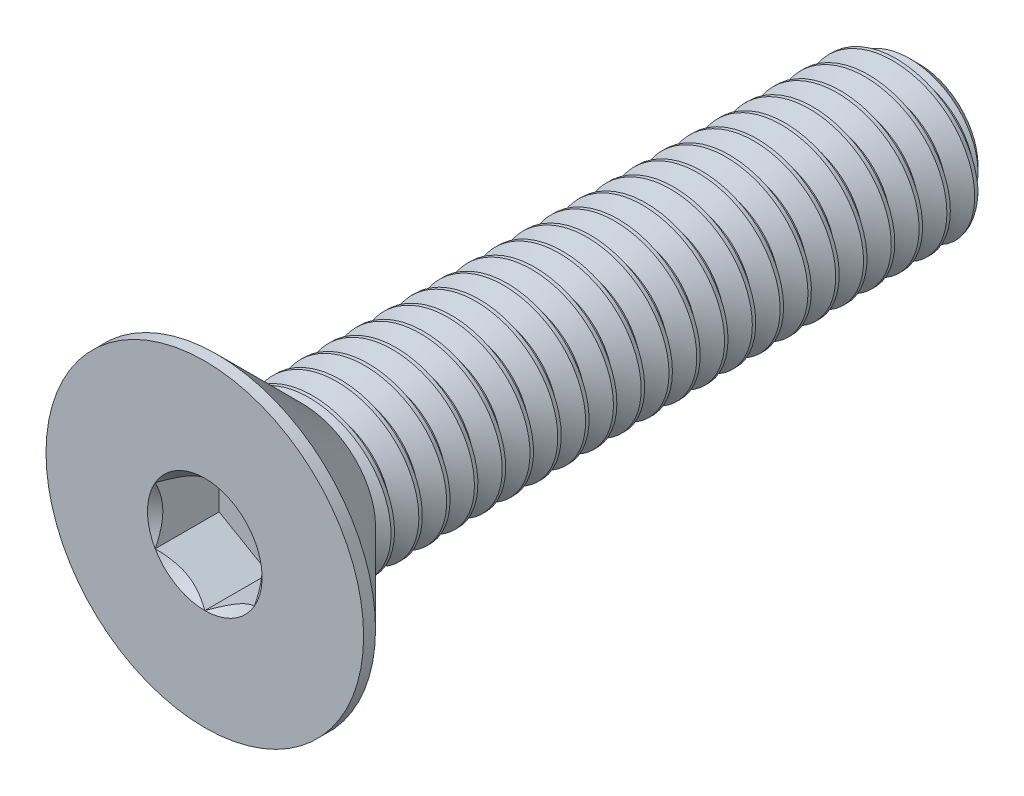
SolidWorks part; units mm, degrees
ref_plane "Front" through (0, 0, 0) normal (0, 0, 1) x (1, 0, 0)
ref_plane "Top" through (0, 0, 0) normal (0, 1, 0) x (1, 0, 0)
ref_plane "Right" through (0, 0, 0) normal (1, 0, 0) x (0, 0, -1)
sketch "Sketch1" plane through (0, 0, 0) normal (1, 0, 0) x (0, 0, -1)
  line L0 (0, 4) -> (0.3, 4) construction
  line L1 (0.3, 4) -> (2.3, 2) construction
  line L2 (0, 2) -> (18, 2)
  line L3 (18, 2) -> (18, 0)
  line L4 (18, 0) -> (0, 0)
  line L5 (0, 0) -> (0, 4) construction
  line L6 (0, 4) -> (0, -4) construction
  line L7 (18, 2) -> (18, -2) construction
  line L8 (0, -4) -> (0.3, -4) construction
  line L9 (0.3, -4) -> (2.3, -2) construction
  line L11 (0, 2) -> (0, 0)
  line L12 (2.3, 2) -> (2.3, 0) construction
  dimension "Head Ht" = 2.3
  dimension "Head Dia" = 8
  dimension "Dia" = 4
  dimension "Lg" = 18
  dimension "Head Angle" = 90
revolve "Revolve1" add sketch "Sketch1" angle 360 mid plane about L4
sketch "Sketch3" plane through (0, 0, -18) normal (0, 0, -1) x (-1, 0, 0)
  circle A0 centre (0, 0) radius 2
curve "Helix/Spiral1" pitch 0.7 height 18 radius 2 centre (0, 0, -18) axis (0, 0, 1) start towards (0, 1, 0)
sketch "Sketch2" plane through (0, 0, 0) normal (1, 0, 0) x (0, 0, -1)
  line L0 (18, 2) -> (18.6125, 2)
  line L1 (18.6125, 2) -> (18.35, 1.5453)
  line L2 (18.35, 1.5453) -> (18.2625, 1.5453)
  line L3 (18.2625, 1.5453) -> (18, 2)
  line L4 (18.1312, 1.7727) -> (18.4812, 1.7727) construction
  dimension "D1" = 60
  dimension "D2" = 0.0875
  dimension "D3" = 0.35
chamfer "Chamfer1" distance 0.525 angle 45 1 edges at (0, 2, -18)
sweep "Cut-Sweep1" cut profiles "Sketch2" path "Helix/Spiral1" align with end faces yes
sketch "Sketch7" plane through (0, 0, 0) normal (1, 0, 0) x (0, 0, -1)
  line L0 (0, 4) -> (0.3, 4) construction
  line L1 (0.3, 4) -> (2.3, 2) construction
  line L2 (0, 4) -> (0.3, 4)
  line L3 (0.3, 4) -> (2.3, 2)
  line L4 (2.3, 2) -> (2.3, 0) construction
  line L5 (2.3, 2) -> (2.3, 0)
  line L7 (0, 0) -> (0, 4) construction
  line L8 (0, 0) -> (0, 4)
  line L9 (0, 0) -> (2.3, 0)
  line L10 (4.4, 0) -> (-4.4, 0) construction
revolve "Revolve2" add sketch "Sketch7" angle 360 mid plane about L9
ref_plane "Plane1" through (0, 0, -2.3) normal (0, 0, 1) x (1, 0, 0)
sketch "Sketch8" plane through (0, 0, -2.3) normal (0, 0, 1) x (1, 0, 0)
  circle A0 centre (0, 0) radius 2
extrude "Boss-Extrude1" add sketch "Sketch8" against normal through all draft 45
sketch "Sketch5" plane through (0, 0, 0) normal (0, 0, 1) x (1, 0, 0)
  line L1 (1.25, -0.7217) -> (1.25, 0.7217)
  line L2 (1.25, 0.7217) -> (0, 1.4434)
  line L3 (0, 1.4434) -> (-1.25, 0.7217)
  line L4 (-1.25, 0.7217) -> (-1.25, -0.7217)
  line L5 (-1.25, -0.7217) -> (0, -1.4434)
  line L6 (0, -1.4434) -> (1.25, -0.7217)
  circle A0 centre (0, 0) radius 1.25 construction
  dimension "Hex" = 2.5
extrude "Cut-Extrude2" cut sketch "Sketch5" against normal blind 1.61
sketch "Sketch6" plane through (0, 0, 0) normal (0, 0, 1) x (1, 0, 0)
  circle A0 centre (0, 0) radius 1.4434
extrude "Cut-Extrude3" cut sketch "Sketch6" against normal blind 1.61 draft 45
sketch "Sketch9" [suppressed] plane through (0, 0, -5.5) normal (0, 0, 1) x (1, 0, 0)
  circle A1 centre (0, 0) radius 5
  circle A2 centre (0, 0) radius 5
  point P0 (0, 5)
  dimension "D1" = 0
extrude "Boss-Extrude2" [suppressed] add sketch "Sketch9" against normal offset from surface (18.5 mm away) 26 up to face at (0, 1.475, -18)
fillet "Fillet1" [suppressed] radius 0.4
sketch "Sketch10" plane through (0, 0, 0) normal (1, 0, 0) x (0, 0, -1)
  line L0 (18, 2) -> (18, -2) construction
  point P0 (16.95, -2)
  dimension "D1" = 1.05
equation "\"D3@Helix/Spiral1\" = \"Lg@Sketch1\""
equation "\"D2@Sketch2\" = \"D4@Helix/Spiral1\" * .125"
equation "\"D3@Sketch2\" = \"D4@Helix/Spiral1\" * .5"
equation "\"D1@Chamfer1\" = \"D4@Helix/Spiral1\" * .75"
equation "\"D1@Cut-Extrude2\" = \"Head Ht@Sketch1\" * .7"
equation "\"D1@Sketch10\" = \"D4@Helix/Spiral1\" * 1.5"
equation "\"D1@Cut-Extrude3\" = \"D1@Cut-Extrude2\""
equation "\"D1@Fillet1\" = \"Dia@Sketch1\" * .1"
